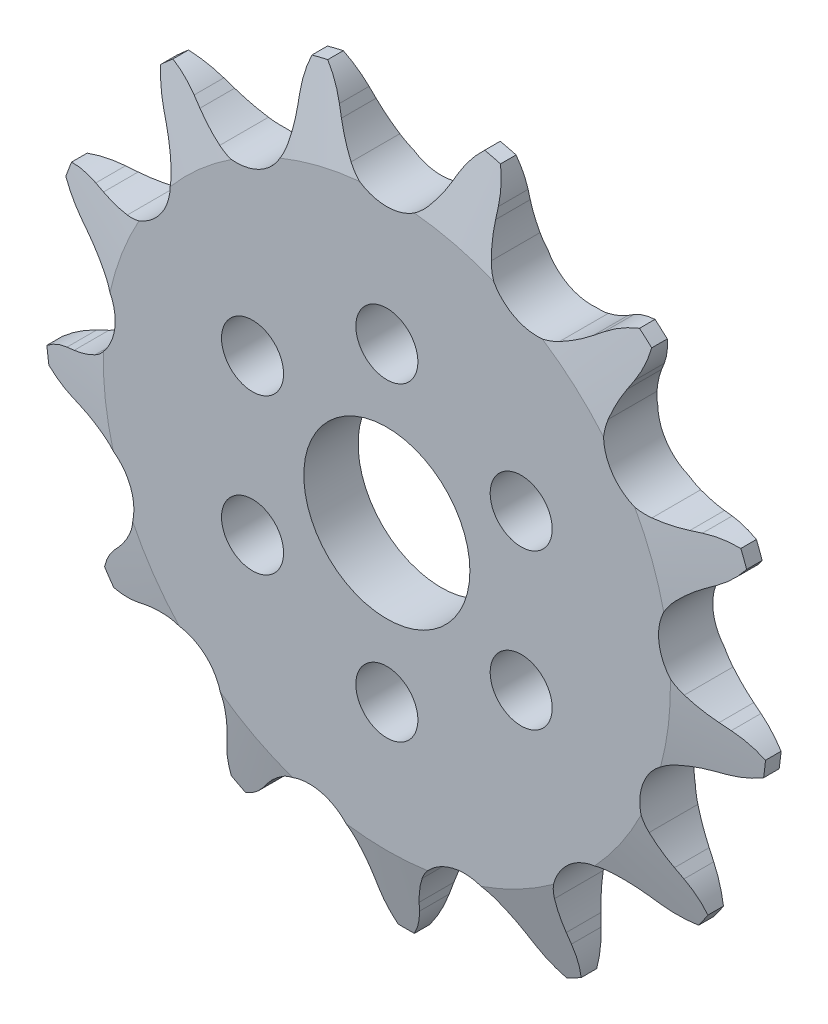
SolidWorks part; units mm, degrees
material "AISI 4130 Steel, annealed at 865C"
ref_plane "Front Plane" through (0, 0, 0) normal (0, 0, 1) x (1, 0, 0)
ref_plane "Top Plane" through (0, 0, 0) normal (0, 1, 0) x (1, 0, 0)
ref_plane "Right Plane" through (0, 0, 0) normal (1, 0, 0) x (0, 0, -1)
sketch "Sketch0" plane through (0, 0, 0) normal (0, 0, 1) x (1, 0, 0)
  line L0 (7.9375, -32.2037) -> (0, 0) construction
  line L1 (0, 0) -> (21.9941, -24.8262) construction
  line L2 (0, 0) -> (-7.9375, -32.2037) construction
  line L3 (7.9375, -32.2037) -> (21.9941, -24.8262) construction
  line L4 (7.9375, -32.2037) -> (-7.9375, -32.2037) construction
  line L5 (13.9545, -31.0679) -> (13.2815, -30.2592)
  line L6 (7.9375, -32.2037) -> (0, -34.1601) construction
  line L7 (2.0819, -33.9942) -> (2.302, -32.9654)
  line L8 (0, -32.2037) -> (0, -36.9662) construction
  line L9 (10.986, -28.0897) -> (3.0984, -38.7342) construction
  line L10 (0, 0) -> (0, -32.2037) construction
  line L11 (13.2815, -30.2592) -> (3.0984, -38.7342) construction
  line L12 (0, -36.9662) -> (0, -38.0102) construction
  line L13 (20.5322, -25.5935) -> (13.9545, -31.0679) construction
  circle A0 centre (0, 0) radius 36.9662 construction
  circle A1 centre (0, 0) radius 33.1675 construction
  arc A2 (-7.9261, -40.603) -> (25.8874, -32.2687) centre (0, 0) ccw
  circle A3 centre (0, 0) radius 38.0102 construction
  circle A4 centre (7.9375, -32.2037) radius 5.08 construction
  arc A7 (10.986, -28.0897) -> (3.3263, -29.9776) centre (7.9375, -32.2037) ccw
  circle A8 centre (7.9375, -32.2037) radius 5.1204 construction
  arc A9 (13.9545, -31.0679) -> (25.8874, -32.2687) centre (20.5322, -25.5935) ccw
  arc A10 (13.2815, -30.2592) -> (10.986, -28.0897) centre (3.0984, -38.7342) ccw
  arc A11 (2.0819, -33.9942) -> (-7.9261, -40.603) centre (-6.2865, -32.2037) cw
  arc A12 (2.302, -32.9654) -> (3.3263, -29.9776) centre (15.2572, -35.7373) cw
  dimension "D1" = 5.1204
  dimension "R" = 5.1204
sketch "Sketch1" plane through (0, 0, 0) normal (1, 0, 0) x (0, 0, -1)
  line L0 (2.7781, 0) -> (-2.7781, 0)
  line L1 (-2.7781, 0) -> (-2.7781, 29.0287)
  line L2 (-2.7781, 29.0287) -> (-0.7937, 36.9662)
  line L3 (-0.7937, 36.9662) -> (0.7937, 36.9662)
  line L4 (0.7937, 36.9662) -> (2.7781, 29.0287)
  line L5 (2.7781, 29.0287) -> (2.7781, 0)
  line L7 (0, 36.9662) -> (0, 0) construction
  line L8 (-2.7781, 29.0287) -> (2.7781, 29.0287) construction
  line L9 (0, 36.9662) -> (0, -36.9662) construction
  line L10 (-2.7781, 29.0287) -> (-2.7781, 36.9662) construction
  line L11 (-2.7781, 36.9662) -> (-0.7937, 36.9662) construction
  line L12 (0.7937, 36.9662) -> (2.7781, 36.9662) construction
  line L13 (2.7781, 36.9662) -> (2.7781, 29.0287) construction
revolve "Revolve1" add sketch "Sketch1" angle 360 mid plane about L0
extrude "Cut-Extrude1" cut sketch "Sketch0" against normal through all and the other way through all
pattern_circular "CirPattern1" count 13 over 360 about axis through (0, 0, -2.7781) along (0, 0, -1) of "Cut-Extrude1"
sketch "Sketch2" plane through (0, 0, 0) normal (0, 0, 1) x (1, 0, 0)
  circle A0 centre (0, 0) radius 7.9375 construction
  circle A1 centre (0, 0) radius 30.1625
  circle A2 centre (0, 0) radius 36.957 construction
  dimension "Bore" = 15.875
  dimension "Hub Dia." = 60.325
  dimension "OD" = 73.914
sketch "Sketch3" plane through (0, 0, 0) normal (0, 0, 1) x (1, 0, 0)
  circle A1 centre (0, 0) radius 8.5
  circle A2 centre (0, 0) radius 36.957 construction
  circle A3 centre (0, 0) radius 36.957
  dimension "D1" = 17
extrude "Cut-Extrude2" cut sketch "Sketch3" along normal through all and the other way through all flip side to cut
sketch "Sketch4" plane through (0, 0, -2.7781) normal (0, 0, -1) x (-1, 0, 0)
  line L0 (0, 0) -> (0, 15.875) construction
  circle A0 centre (0, 15.875) radius 3.175
  circle A1 centre (13.7482, 7.9375) radius 3.175
  circle A2 centre (13.7482, -7.9375) radius 3.175
  circle A3 centre (0, -15.875) radius 3.175
  circle A4 centre (-13.7482, -7.9375) radius 3.175
  circle A5 centre (-13.7482, 7.9375) radius 3.175
  point P17 (0, 0)
  dimension "D1" = 6
extrude "Cut-Extrude3" cut sketch "Sketch4" against normal through all
sketch "Sketch5" plane through (0, 0, 2.7781) normal (0, 0, 1) x (1, 0, 0)
  line L0 (0, 0) -> (8.5, 0) construction
  line L1 (8.5, 0) -> (11, 0) construction
  circle A0 centre (0, 0) radius 11 construction
  circle A1 centre (0, 0) radius 8.5 construction
sketch "Sketch6" plane through (0, 0, -2.7781) normal (0, 0, -1) x (-1, 0, 0)
  circle A0 centre (0, 0) radius 28.024 construction
  circle A1 centre (0, 0) radius 24.2521 construction
ref_plane "Plane1" through (-29.6883, 20.4924, 0) normal (-0.823, 0.5681, 0) x (0, 0, 1)
ref_plane "Plane2" through (-35.811, 4.3482, 0) normal (-0.9927, 0.1205, 0) x (0, 0, 1)
ref_plane "Plane3" through (-33.7298, -12.792, 0) normal (-0.935, -0.3546, 0) x (0, 0, 1)
ref_plane "Plane4" through (-23.9215, -27.0018, 0) normal (-0.6631, -0.7485, 0) x (-0.7485, 0.6631, 0)
ref_plane "Plane5" through (-8.6331, -35.0258, 0) normal (-0.2393, -0.9709, 0) x (-0.9709, 0.2393, 0)
sketch "Sketch7" plane through (-29.6883, 20.4924, 0) normal (-0.823, 0.5681, 0) x (0, 0, 1)
  line L0 (-6.5106, 0) -> (7.7601, 0)
sketch "Sketch8" plane through (-35.811, 4.3482, 0) normal (-0.9927, 0.1205, 0) x (0, 0, 1)
  line L0 (-7.786, 0) -> (10.2102, 0)
sketch "Sketch9" plane through (-33.7298, -12.792, 0) normal (-0.935, -0.3546, 0) x (0, 0, 1)
  line L0 (-7.6671, 0) -> (14.0341, 0)
  line L1 (-2.7781, 0) -> (2.7781, 0) construction
sketch "Sketch10" plane through (-23.9215, -27.0018, 0) normal (-0.6631, -0.7485, 0) x (-0.7485, 0.6631, 0)
  line L0 (0, -3.5829) -> (0, 5.4944)
sketch "Sketch11" plane through (-8.6331, -35.0258, 0) normal (-0.2393, -0.9709, 0) x (-0.9709, 0.2393, 0)
  line L0 (0, -5.4358) -> (0, 8.5188)
split line "Split Line7"
split line "Split Line8"
split line "Split Line9"
split line "Split Line10"
split line "Split Line11"
ref_plane "Motor Sprocket Middle Plane" through (0, 0, -0.0019) normal (0, 0, 1) x (1, 0, 0)
equation "\"360/N@Sketch0\" = 360/\"Teeth@CirPattern1\""
equation "\"Ds@Sketch0\" = 1.005 * \"Dr@Sketch0\" + 0.003"
equation "\"R@Sketch0\" = 1/2 * \"Ds@Sketch0\""
equation "\"A@Sketch0\" = 35 +  ( 60 / \"Teeth@CirPattern1\" ) "
equation "\"B@Sketch0\" = 18 -  ( 56 / \"Teeth@CirPattern1\" )"
equation "\"ac@Sketch0\" = 0.8 * \"Dr@Sketch0\""
equation "\"ab@Sketch0\" = 1.4 * \"Dr@Sketch0\""
equation "\"J@Sketch0\" = 0.3 * \"Pitch@Sketch0\""
equation "\"h@Sketch1\" = \"Pitch@Sketch0\" / 2"
equation "\"g@Sketch1\" = \"h@Sketch1\" / 4"
